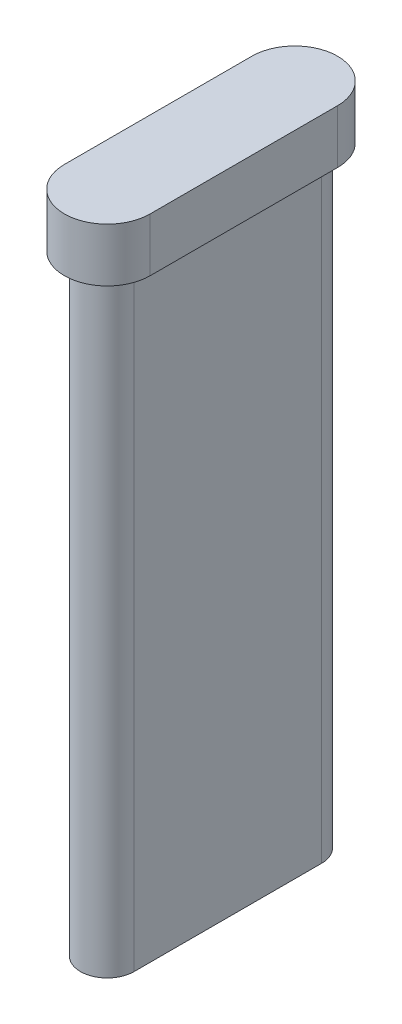
SolidWorks part; units mm, degrees
material "K110"
ref_plane "Front Plane" through (0, 0, 0) normal (0, 0, 1) x (1, 0, 0)
ref_plane "Top Plane" through (0, 0, 0) normal (0, 1, 0) x (1, 0, 0)
ref_plane "Right Plane" through (0, 0, 0) normal (1, 0, 0) x (0, 0, -1)
sketch "Sketch1" plane through (0, 0, 0) normal (0, 1, 0) x (1, 0, 0)
  line L0 (0, -8.75) -> (0, 8.75) construction
  line L1 (-2.5, -8.75) -> (-2.5, 8.75)
  line L2 (2.5, -8.75) -> (2.5, 8.75)
  arc A0 (-2.5, -8.75) -> (2.5, -8.75) centre (0, -8.75) ccw
  arc A1 (2.5, 8.75) -> (-2.5, 8.75) centre (0, 8.75) ccw
  point P2 (0, 0)
  dimension "D2" = 2.5
  dimension "D1" = 17.5
extrude "Boss-Extrude1" add sketch "Sketch1" against normal blind 62
sketch "Sketch2" plane through (0, 0, 0) normal (0, 1, 0) x (1, 0, 0)
  line L4 (4, -8.75) -> (4, 8.75)
  line L5 (-4, 8.75) -> (-4, -8.75)
  line L6 (4, -8.75) -> (4, 8.75)
  line L7 (-4, 8.75) -> (-4, -8.75)
  arc A4 (4, 8.75) -> (-4, 8.75) centre (0, 8.75) ccw
  arc A5 (-4, -8.75) -> (4, -8.75) centre (0, -8.75) ccw
  arc A6 (4, 8.75) -> (-4, 8.75) centre (0, 8.75) ccw
  arc A7 (-4, -8.75) -> (4, -8.75) centre (0, -8.75) ccw
  dimension "D1" = 1.5
extrude "Boss-Extrude2" add sketch "Sketch2" against normal blind 5
